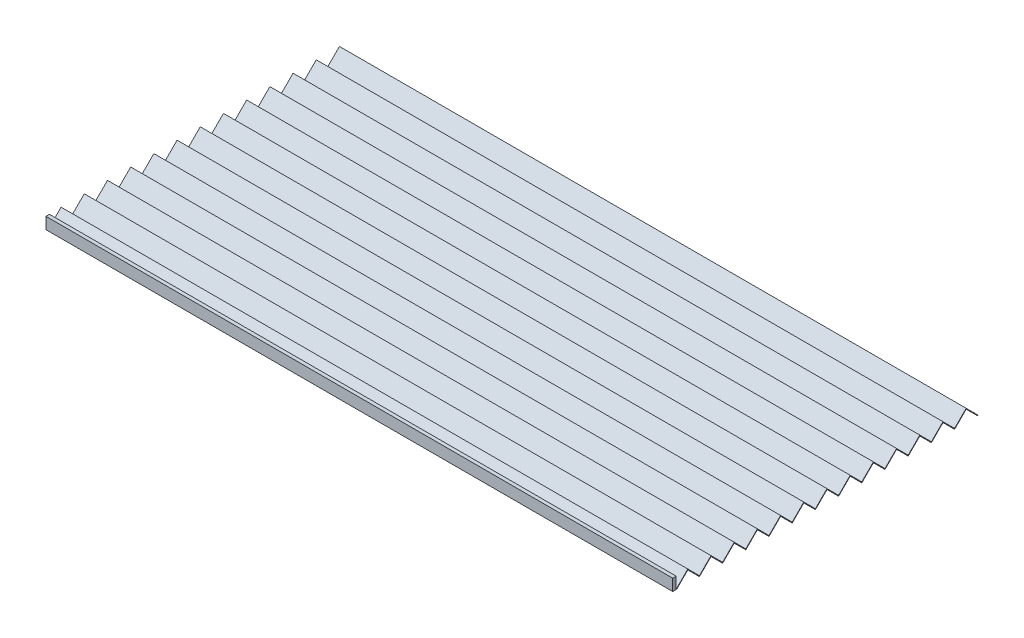
SolidWorks part; units mm, degrees
ref_plane "Front Plane" through (0, 0, 0) normal (0, 0, 1) x (1, 0, 0)
ref_plane "Top Plane" through (0, 0, 0) normal (0, 1, 0) x (1, 0, 0)
ref_plane "Right Plane" through (0, 0, 0) normal (1, 0, 0) x (0, 0, -1)
sketch "Sketch2" plane through (0, 0, 0) normal (0, 0, 1) x (1, 0, 0)
  line L1 (-270, 10) -> (270, 10)
  line L2 (-270, 10) -> (-270, 0)
  line L3 (-270, 0) -> (270, 0)
  line L4 (270, 10) -> (270, 0)
  point P4 (0, 0)
  dimension "D1" = 10
  dimension "D2" = 540
extrude "Boss-Extrude1" add sketch "Sketch2" along normal blind 3
sketch "Sketch3" plane through (270, 0, 0) normal (1, 0, 0) x (0, 0, -1)
  line L0 (0, 10) -> (259.8317, 10) construction
  line L1 (0, 0) -> (259.8317, 0) construction
  line L2 (259.8317, 10) -> (259.8317, 0) construction
  line L3 (0, 0) -> (9.9935, 10)
  line L4 (9.9935, 10) -> (19.9871, 0)
  line L5 (19.9871, 0) -> (29.9806, 10)
  line L6 (29.9806, 10) -> (39.9741, 0)
  line L7 (39.9741, 0) -> (49.9676, 10)
  line L8 (49.9676, 10) -> (59.9612, 0)
  line L9 (59.9612, 0) -> (69.9547, 10)
  line L10 (69.9547, 10) -> (79.9482, 0)
  line L11 (79.9482, 0) -> (89.9417, 10)
  line L12 (89.9417, 10) -> (99.9353, 0)
  line L13 (99.9353, 0) -> (109.9288, 10)
  line L14 (109.9288, 10) -> (119.9223, 0)
  line L15 (119.9223, 0) -> (129.9158, 10)
  line L16 (129.9158, 10) -> (139.9094, 0)
  line L17 (139.9094, 0) -> (149.9029, 10)
  line L18 (149.9029, 10) -> (159.8964, 0)
  line L20 (159.8964, 0) -> (169.8899, 10)
  line L21 (169.8899, 10) -> (179.8835, 0)
  line L22 (179.8835, 0) -> (189.877, 10)
  line L23 (189.877, 10) -> (199.8705, 0)
  line L24 (199.8705, 0) -> (209.864, 10)
  line L25 (209.864, 10) -> (219.8576, 0)
  line L26 (219.8576, 0) -> (229.8511, 10)
  line L27 (229.8511, 10) -> (239.8446, 0)
  line L28 (239.8446, 0) -> (249.8381, 10)
  line L29 (249.8381, 10) -> (259.8317, 0)
  line L30 (259.8317, 10) -> (259.8317, 0) construction
extrude "Extrude-Thin1" add sketch "Sketch3" against normal through all thin thin type mid plane wall 0.5
